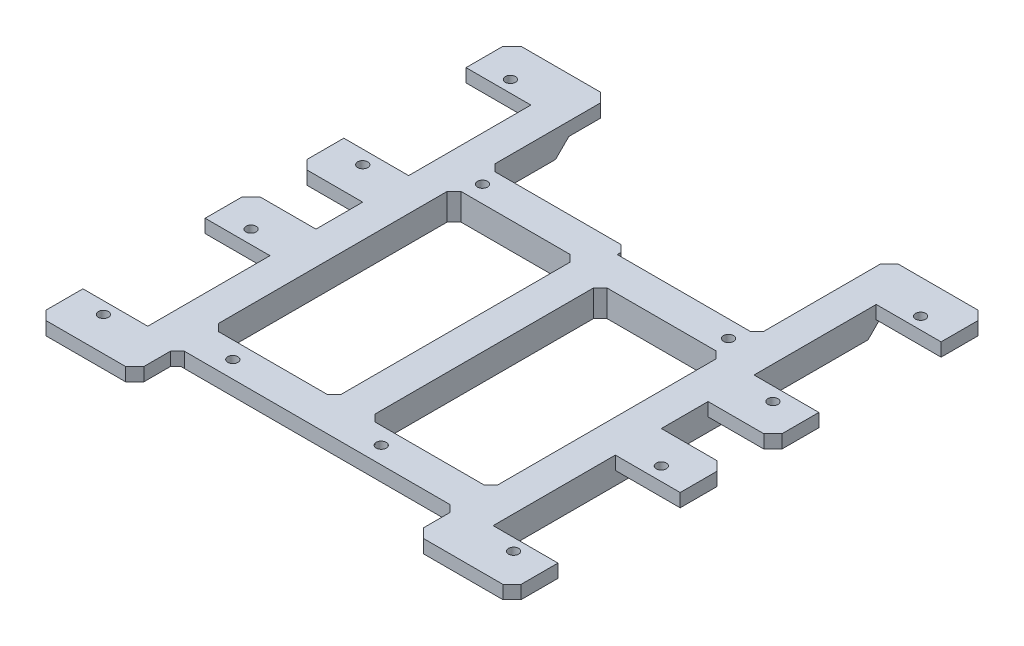
SolidWorks part; units mm, degrees
other "Markup1"
sketch "Sketch8" plane through (-44.7, 2.5, -44.7) normal (0, 1, 0) x (1, 0, 0)
sketch "Sketch10" plane through (-44.7, 2.5, -44.7) normal (0, 1, 0) x (1, 0, 0)
sketch "Sketch12" plane through (-44.7, 2.5, -44.7) normal (0, 1, 0) x (1, 0, 0)
other "Markup2"
sketch "Sketch9" plane through (-44.7, 2.5, -44.7) normal (0, 1, 0) x (1, 0, 0)
sketch "Sketch11" plane through (-44.7, 2.5, -44.7) normal (0, 1, 0) x (1, 0, 0)
sketch "Sketch13" plane through (-44.7, 2.5, -44.7) normal (0, 1, 0) x (1, 0, 0)
ref_plane "Front Plane" through (0, 0, 0) normal (0, 0, 1) x (1, 0, 0)
ref_plane "Top Plane" through (0, 0, 0) normal (0, 1, 0) x (1, 0, 0)
ref_plane "Right Plane" through (0, 0, 0) normal (1, 0, 0) x (0, 0, -1)
sketch "Sketch1" plane through (0, 0, 0) normal (0, 1, 0) x (1, 0, 0)
  line L0 (0, 44.7) -> (0, -44.7) construction
  line L1 (44.7, -44.7) -> (-44.7, -44.7)
  line L2 (44.7, -44.7) -> (44.7, 44.7)
  line L3 (44.7, 44.7) -> (-44.7, 44.7)
  line L4 (-44.7, -44.7) -> (-44.7, 44.7)
  line L5 (44.7, -44.7) -> (-44.7, 44.7) construction
  line L6 (44.7, 44.7) -> (-44.7, -44.7) construction
  circle A4 centre (-38.6, 38.3) radius 0.95
  circle A5 centre (-38.6, 10.5) radius 0.95
  circle A6 centre (-38.6, -10.5) radius 0.95
  circle A7 centre (-38.6, -38.3) radius 0.95
  circle A16 centre (38.6, -38.3) radius 0.95
  circle A17 centre (38.6, -10.5) radius 0.95
  circle A18 centre (38.6, 10.5) radius 0.95
  circle A19 centre (38.6, 38.3) radius 0.95
  point P0 (0, 0)
  point P6 (0, 0)
  dimension "D17" = 1.9
  dimension "D20" = 1.9
  dimension "D23" = 1.9
  dimension "D26" = 1.9
  dimension "D1" = 89.4
  dimension "D2" = 89.4
  dimension "D18" = 6.4
  dimension "D19" = 6.1
  dimension "D21" = 6.1
  dimension "D22" = 27.8
  dimension "D24" = 6.1
  dimension "D25" = 6.4
  dimension "D27" = 6.1
  dimension "D28" = 27.8
extrude "Boss-Extrude1" add sketch "Sketch1" along normal blind 2.5
sketch "Sketch5" plane through (0, 0, 0) normal (0, -1, 0) x (1, 0, 0)
  line L1 (32.5, -37) -> (-32.5, -37)
  line L2 (32.5, -37) -> (32.5, 37)
  line L3 (32.5, 37) -> (-32.5, 37)
  line L4 (-32.5, -37) -> (-32.5, 37)
  line L5 (32.5, -37) -> (-32.5, 37) construction
  line L6 (32.5, 37) -> (-32.5, -37) construction
  point P0 (0, 0)
  dimension "D1" = 65
  dimension "D2" = 74
extrude "Boss-Extrude3" add sketch "Sketch5" along normal blind 2.5
sketch "Sketch7" plane through (0, 2.5, 0) normal (0, 1, 0) x (1, 0, 0)
  line L1 (30.5, -35) -> (-30.5, -35) construction
  line L2 (30.5, -35) -> (30.5, 35) construction
  line L3 (30.5, 35) -> (-30.5, 35) construction
  line L4 (-30.5, -35) -> (-30.5, 35) construction
  line L5 (30.5, -35) -> (-30.5, 35) construction
  line L6 (30.5, 35) -> (-30.5, -35) construction
  circle A0 centre (-24.15, 18.595) radius 0.95
  circle A1 centre (24.15, 16.605) radius 0.95
  circle A2 centre (-19.07, -33.475) radius 0.95
  circle A3 centre (8.86, -33.475) radius 0.95
  point P0 (0, 0)
  dimension "D3" = 1.9
  dimension "D6" = 1.9
  dimension "D9" = 1.9
  dimension "D12" = 1.9
  dimension "D13" = 3.05
  dimension "D1" = 70
  dimension "D2" = 61
  dimension "D4" = 6.35
  dimension "D5" = 52.07
  dimension "D7" = 6.35
  dimension "D8" = 50.08
  dimension "D10" = 3.05
  dimension "D11" = 11.43
  dimension "D14" = 21.64
extrude "Cut-Extrude2" cut sketch "Sketch7" against normal blind 4
sketch "Sketch2" plane through (0, 2.5, 0) normal (0, 1, 0) x (1, 0, 0)
  line L0 (44.7, 44.7) -> (-44.7, 44.7) construction
  line L1 (-44.7, 40.6) -> (-32.5, 40.6) construction
  line L2 (-44.7, 40.6) -> (-44.7, 8.5) construction
  line L3 (-44.7, 8.5) -> (-32.5, 8.5) construction
  line L4 (-32.5, 40.6) -> (-32.5, 8.5) construction
  line L5 (-44.7, 40.6) -> (-32.5, 8.5) construction
  line L6 (-44.7, 8.5) -> (-32.5, 40.6) construction
  line L7 (-44.7, 44.7) -> (-44.7, -44.7) construction
  line L8 (0, 44.7) -> (0, -44.7) construction
  line L9 (-44.7, -44.7) -> (44.7, -44.7) construction
  line L10 (-44.7, 0) -> (44.7, 0) construction
  line L11 (44.7, -44.7) -> (44.7, 44.7) construction
  line L12 (-44.7, -8.5) -> (-32.5, -40.6) construction
  line L13 (-44.7, -40.6) -> (-32.5, -8.5) construction
  line L14 (-32.5, -40.6) -> (-32.5, -8.5) construction
  line L15 (-44.7, -8.5) -> (-32.5, -8.5) construction
  line L16 (-44.7, -40.6) -> (-44.7, -8.5) construction
  line L17 (-44.7, -40.6) -> (-32.5, -40.6) construction
  line L18 (44.7, -40.6) -> (32.5, -40.6) construction
  line L19 (44.7, -40.6) -> (44.7, -8.5) construction
  line L20 (44.7, -8.5) -> (32.5, -8.5) construction
  line L21 (32.5, -40.6) -> (32.5, -8.5) construction
  line L22 (44.7, -40.6) -> (32.5, -8.5) construction
  line L23 (44.7, -8.5) -> (32.5, -40.6) construction
  line L24 (44.7, 8.5) -> (32.5, 40.6) construction
  line L25 (44.7, 40.6) -> (32.5, 8.5) construction
  line L26 (32.5, 40.6) -> (32.5, 8.5) construction
  line L27 (44.7, 8.5) -> (32.5, 8.5) construction
  line L28 (44.7, 40.6) -> (44.7, 8.5) construction
  line L29 (44.7, 40.6) -> (32.5, 40.6) construction
  line L31 (-32.5, 13.05) -> (-44.7, 13.05)
  line L32 (-32.5, 13.05) -> (-32.5, 36.05)
  line L33 (-32.5, 36.05) -> (-44.7, 36.05)
  line L34 (-44.7, 13.05) -> (-44.7, 36.05)
  line L35 (-32.5, 13.05) -> (-44.7, 36.05) construction
  line L36 (-32.5, 36.05) -> (-44.7, 13.05) construction
  line L48 (44.7, 44.7) -> (-44.7, 44.7) construction
  line L49 (-26.3, 44.7) -> (26.3, 44.7)
  line L50 (-26.3, 44.7) -> (-26.3, 21.795)
  line L51 (-26.3, 21.795) -> (0, 21.795)
  line L52 (26.3, 44.7) -> (26.3, 24.23)
  line L53 (44.7, -44.7) -> (-44.7, -44.7) construction
  line L54 (-26.3, -44.7) -> (26.3, -44.7)
  line L55 (-26.3, -44.7) -> (-26.3, -36.675)
  line L56 (-26.3, -36.675) -> (26.3, -36.675)
  line L57 (26.3, -44.7) -> (26.3, -36.675)
  line L58 (-44.7, -44.7) -> (-44.7, 44.7) construction
  line L59 (-26.3, 15.395) -> (-3.2, 15.395)
  line L60 (-26.3, 15.395) -> (-26.3, -30.275)
  line L61 (-26.3, -30.275) -> (-3.2, -30.275)
  line L62 (-3.2, 15.395) -> (-3.2, -30.275)
  line L63 (3.2, 13.405) -> (26.3, 13.405)
  line L64 (3.2, 13.405) -> (3.2, -30.275)
  line L65 (3.2, -30.275) -> (26.3, -30.275)
  line L66 (26.3, 13.405) -> (26.3, -30.275)
  line L67 (-44.7, 4.4) -> (-32.5, 4.4)
  line L68 (-44.7, 4.4) -> (-44.7, -4.4)
  line L69 (-44.7, -4.4) -> (-32.5, -4.4)
  line L70 (-32.5, 4.4) -> (-32.5, -4.4)
  line L71 (44.7, -44.7) -> (44.7, 44.7) construction
  line L72 (44.7, 4.4) -> (32.5, 4.4)
  line L73 (44.7, 4.4) -> (44.7, -4.4)
  line L74 (44.7, -4.4) -> (32.5, -4.4)
  line L75 (32.5, 4.4) -> (32.5, -4.4)
  line L76 (32.5, 36.05) -> (44.7, 36.05)
  line L78 (26.3, 24.23) -> (26.3, 19.805)
  line L79 (26.3, 19.805) -> (0, 19.805)
  line L80 (0, 21.795) -> (0, 19.805)
  line L81 (44.7, 13.05) -> (44.7, 36.05)
  line L82 (32.5, 13.05) -> (44.7, 13.05)
  line L83 (32.5, 13.05) -> (32.5, 36.05)
  line L84 (32.5, -13.05) -> (32.5, -36.05)
  line L85 (32.5, -13.05) -> (44.7, -13.05)
  line L86 (44.7, -13.05) -> (44.7, -36.05)
  line L87 (32.5, -36.05) -> (44.7, -36.05)
  line L88 (-32.5, -36.05) -> (-44.7, -36.05)
  line L89 (-44.7, -13.05) -> (-44.7, -36.05)
  line L90 (-32.5, -13.05) -> (-44.7, -13.05)
  line L91 (-32.5, -13.05) -> (-32.5, -36.05)
  point P0 (-38.6, 24.55)
  point P5 (-38.6, 40.6)
  point P23 (-38.6, -24.55)
  point P32 (38.6, -24.55)
  point P33 (38.6, 24.55)
  point P34 (-38.6, 24.55)
  dimension "D1" = 32.1
  dimension "D2" = 12.2
  dimension "D3" = 4.1
  dimension "D4" = 23
  dimension "D5" = 3.2
  dimension "D6" = 3.2
  dimension "D7" = 3.2
  dimension "D8" = 3.2
  dimension "D9" = 6.2
  dimension "D10" = 6.2
  dimension "D11" = 6.2
  dimension "D12" = 6.2
  dimension "D13" = 6.2
  dimension "D14" = 6.2
  dimension "D15" = 3.2
  dimension "D16" = 3.2
  dimension "D17" = 3.2
  dimension "D18" = 3.2
  dimension "D19" = 3.2
  dimension "D20" = 4.1
  dimension "D21" = 4.1
  dimension "D22" = 6.2
  dimension "D23" = 4.1
  dimension "D24" = 4.1
  dimension "D25" = 6.2
extrude "Cut-Extrude1" cut sketch "Sketch2" against normal through all both and the other way through all
chamfer "Chamfer2" distance 1.3 angle 45 1 edges at (0, 0, -21.795)
chamfer "Chamfer3" distance 1.3 angle 45 12 edges at (-26.3, 0, -21.795) (26.3, 0, 36.675) (-26.3, 0, 36.675) (-26.3, 0, 30.275) (-3.2, 0, 30.275) (3.2, 0, 30.275) (26.3, 0, 30.275) (-3.2, 0, -15.395) (3.2, 0, -13.405) (26.3, 0, -13.405) (26.3, 0, -19.805) (-26.3, 0, -15.395)
chamfer "Chamfer4" distance 1.7 angle 45 12 edges at (44.7, 1.25, 4.4) (44.7, 1.25, -4.4) (-44.7, 1.25, 4.4) (-44.7, 1.25, -4.4) (44.7, 1.25, 44.7) (26.3, 1.25, 44.7) (-26.3, 1.25, 44.7) (-44.7, 1.25, 44.7) (44.7, 1.25, -44.7) (26.3, 1.25, -44.7) (-26.3, 1.25, -44.7) (-44.7, 1.25, -44.7)
chamfer "Chamfer5" distance 2.5 angle 45 3 edges at (28.9125, -2.5, 37) (29.4, -2.5, -37) (-29.4, -2.5, -37)
